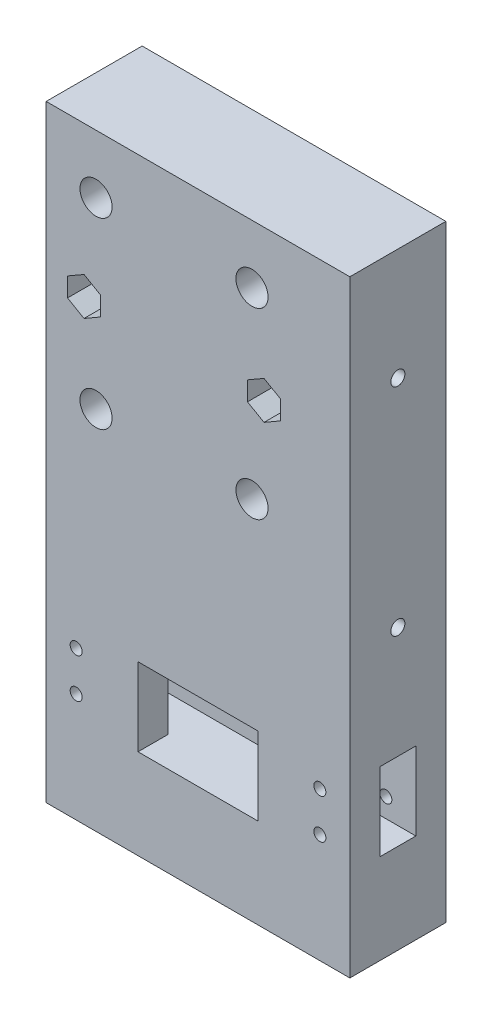
SolidWorks part; units mm, degrees
other "Markup1"
sketch "Sketch8" plane through (21.3115, 25, 0) normal (0.306, 0.1864, -0.9336) x (-0.9512, 0.0181, -0.3081)
ref_plane "Front Plane" through (0, 0, 0) normal (0, 0, 1) x (1, 0, 0)
ref_plane "Top Plane" through (0, 0, 0) normal (0, 1, 0) x (1, 0, 0)
ref_plane "Right Plane" through (0, 0, 0) normal (1, 0, 0) x (0, 0, -1)
sketch "Sketch1" plane through (0, 0, 0) normal (0, 0, 1) x (1, 0, 0)
  line L0 (0, 25) -> (0, -25) construction
  line L1 (21.3115, 25) -> (-21.3115, 25)
  line L2 (21.3115, 25) -> (21.3115, -25)
  line L3 (21.3115, -25) -> (-21.3115, -25)
  line L4 (-21.3115, 25) -> (-21.3115, -25)
  line L5 (21.3115, 25) -> (-21.3115, -25) construction
  line L6 (21.3115, -25) -> (-21.3115, 25) construction
  line L7 (-21.3115, 0) -> (21.3115, 0) construction
  circle A0 centre (-13, -15.25) radius 2.677
  circle A1 centre (13, -15.25) radius 2.677
  circle A2 centre (13, 15.25) radius 2.677
  circle A3 centre (-13, 15.25) radius 2.677
  point P0 (0, 0)
  dimension "D1" = 30.5
  dimension "D2" = 26
  dimension "D3" = 50
extrude "Boss-Extrude1" add sketch "Sketch1" along normal blind 16
sketch "Sketch2" plane through (0, 0, 0) normal (0, 0, 1) x (1, 0, 0)
  circle A0 centre (0, 0) radius 11.04
  dimension "D1" = 22.08
extrude "Cut-Extrude2" cut sketch "Sketch2" along normal blind 11
sketch "Sketch3" plane through (0, 0, 0) normal (0, 0, -1) x (-1, 0, 0)
  line L0 (0, 0) -> (-18.0234, 0) construction
  line L1 (0, 0) -> (0, 5.0894) construction
  circle A0 centre (-15, 0) radius 1.75
  circle A1 centre (15, 0) radius 1.75
  dimension "D1" = 15
  dimension "D2" = 3.5
extrude "Cut-Extrude3" cut sketch "Sketch3" against normal blind 10
sketch "Sketch9" plane through (0, 0, 0) normal (0, 0, -1) x (-1, 0, 0)
  line L0 (0, -11.04) -> (0, 11.04) construction
  line L1 (-15, 3.1754) -> (-17.75, 1.5877)
  line L2 (-17.75, 1.5877) -> (-17.75, -1.5877)
  line L3 (-17.75, -1.5877) -> (-15, -3.1754)
  line L4 (-15, -3.1754) -> (-12.25, -1.5877)
  line L5 (-12.25, -1.5877) -> (-12.25, 1.5877)
  line L6 (-12.25, 1.5877) -> (-15, 3.1754)
  line L7 (12.25, 1.5877) -> (15, 3.1754)
  line L8 (12.25, -1.5877) -> (12.25, 1.5877)
  line L9 (15, -3.1754) -> (12.25, -1.5877)
  line L10 (17.75, -1.5877) -> (15, -3.1754)
  line L11 (17.75, 1.5877) -> (17.75, -1.5877)
  line L12 (15, 3.1754) -> (17.75, 1.5877)
  circle A0 centre (-15, 0) radius 2.75 construction
  circle A1 centre (0, 0) radius 11.04 construction
  point P1 (-17.75, 0)
  dimension "D1" = 5.5
extrude "Cut-Extrude6" cut sketch "Sketch9" against normal through all from offset 5 offset against normal yes
sketch "Sketch30" plane through (0, -25, 0) normal (0, -1, 0) x (1, 0, 0)
  line L1 (-21.3115, 16) -> (21.3115, 16)
  line L2 (-21.3115, 16) -> (-21.3115, 0)
  line L3 (-21.3115, 0) -> (21.3115, 0)
  line L4 (21.3115, 16) -> (21.3115, 0)
extrude "Boss-Extrude8" add sketch "Sketch30" along normal blind 20.23
sketch "Sketch10" plane through (0, 0, 0) normal (0, 0, 1) x (1, 0, 0)
  line L0 (21.3115, -45.23) -> (-21.3115, -45.23)
  line L2 (-21.3115, -45.23) -> (-21.3115, -61.23)
  line L3 (-21.3115, -61.23) -> (21.3115, -61.23)
  line L4 (21.3115, -61.23) -> (21.3115, -45.23)
  dimension "D1" = 16
extrude "Boss-Extrude2" add sketch "Sketch10" along normal up to surface (16 mm away) up to face at (15, 0, 16)
sketch "Sketch14" plane through (-21.3115, 0, 0) normal (-1, 0, 0) x (0, 0, 1)
  line L0 (16, -61.23) -> (0, -61.23) construction
  line L1 (5, -61.23) -> (11, -61.23)
  line L2 (5, -61.23) -> (5, -48.23)
  line L3 (5, -48.23) -> (11, -48.23)
  line L4 (11, -61.23) -> (11, -48.23)
  line L7 (0, -61.23) -> (16, -61.23) construction
  point P6 (8, -61.23)
  point P7 (8, -61.23)
  dimension "D1" = 13
  dimension "D2" = 6
extrude "Cut-Extrude7" cut sketch "Sketch14" against normal through all
sketch "Sketch16" plane through (21.3115, 0, 0) normal (1, 0, 0) x (0, 0, -1)
  line L0 (-8, -48.23) -> (-8, 25)
  line L1 (-11, -48.23) -> (-5, -48.23) construction
  line L2 (-16, 25) -> (0, 25) construction
  line L4 (-16, 25) -> (0, 25)
  line L5 (-16, 25) -> (-16, -48.23)
  line L6 (-16, -48.23) -> (0, -48.23)
  line L7 (0, 25) -> (0, -48.23)
  line M6 (-11, -48.23) -> (-5, -48.23)
  line M9 (0, -61.23) -> (0, 25)
  line M10 (0, 25) -> (-16, 25)
  line M11 (-16, 25) -> (-16, -61.23)
extrude "Boss-Extrude3" add sketch "Sketch16" along normal blind 8 contours L6 L0 M11 M6 M10 | L6 L0 M6 M9 M10 region at (21.3115, -11.615, 12) region at (21.3115, -11.615, 4)
sketch "Sketch17" plane through (29.3115, 0, 0) normal (1, 0, 0) x (0, 0, -1)
  line L0 (-8, -48.23) -> (-8, 25)
  line L1 (-16, -48.23) -> (0, -48.23) construction
  line L2 (0, 25) -> (-16, 25) construction
  line L3 (-8, -11.615) -> (0, -11.615)
  line L4 (0, -48.23) -> (0, 25) construction
  circle A0 centre (-8, 6.385) radius 1.175
  circle A1 centre (-8, -29.615) radius 1.175
  point P8 (-8, -11.615)
  dimension "D2" = 2.35
  dimension "D1" = 18
extrude "Cut-Extrude9" cut sketch "Sketch17" against normal blind 8 contours L0 A0 | L0 A0 | A1 L0 | A1 L0 region at (29.3115, -29.615, 8.4987) region at (29.3115, 6.385, 8.4987) region at (29.3115, 6.385, 7.5013) region at (29.3115, -29.615, 7.5013)
sketch "Sketch18" plane through (0, 0, 0) normal (0, 0, -1) x (-1, 0, 0)
  line L0 (-25.3115, -48.23) -> (-25.3115, 25)
  line L1 (-29.3115, -48.23) -> (-21.3115, -48.23) construction
  line L2 (-29.3115, 25) -> (21.3115, 25) construction
  line L3 (-25.3115, -11.615) -> (-29.3115, -11.615)
  line L4 (-26.2115, 8.385) -> (-24.4115, 8.385)
  line L5 (-26.2115, 8.385) -> (-26.2115, 4.385)
  line L6 (-26.2115, 4.385) -> (-24.4115, 4.385)
  line L7 (-24.4115, 8.385) -> (-24.4115, 4.385)
  line L8 (-26.2115, 8.385) -> (-24.4115, 4.385) construction
  line L9 (-26.2115, 4.385) -> (-24.4115, 8.385) construction
  line L10 (-29.3115, -48.23) -> (-29.3115, 25) construction
  line L11 (-26.2115, -27.615) -> (-24.4115, -27.615)
  line L12 (-24.4115, -31.615) -> (-24.4115, -27.615)
  line L13 (-26.2115, -31.615) -> (-24.4115, -31.615)
  line L14 (-26.2115, -31.615) -> (-26.2115, -27.615)
  point P6 (-25.3115, 6.385)
  point P11 (-25.3115, -11.615)
  dimension "D1" = 18
  dimension "D2" = 4
  dimension "D3" = 1.8
extrude "Cut-Extrude10" cut sketch "Sketch18" against normal blind 10.2 contours L7 L4 L0 L6 | L5 L6 L0 L4 | L14 L11 L12 L13 region at (25.7615, 6.385, 0) region at (24.8615, 6.385, 0)
sketch "Sketch15" plane through (0, 0, 0) normal (0, 0, -1) x (-1, 0, 0)
  line L0 (21.3115, -61.23) -> (-21.3115, -61.23) construction
  line L1 (-29.3115, -23.2996) -> (21.3115, -23.2996)
  line L2 (-21.3115, -61.23) -> (-21.3115, -48.23)
  line L3 (-29.3115, -48.23) -> (-29.3115, 25) construction
  line L4 (-4, -23.2996) -> (-4, -61.23)
  line L7 (-21.3115, -61.23) -> (-21.3115, -48.23) construction
  line L8 (-21.3115, -48.23) -> (-21.3115, -61.23) construction
  line L9 (-21.3115, -54.73) -> (21.3115, -54.73)
  line L10 (21.3115, 25) -> (21.3115, -61.23) construction
  line L11 (21.3115, -54.73) -> (21.3115, -28)
  line L12 (21.3115, -28) -> (0, -28)
  line L13 (0, -28) -> (0, -61.23)
  circle A2 centre (16.3115, -58.03) radius 1
  circle A4 centre (16.3115, -51.43) radius 1
  point P11 (-21.3115, -61.23)
  dimension "D1" = 5
  dimension "D2" = 3.2
extrude "Cut-Extrude8" cut sketch "Sketch15" against normal through all and the other way through all contours A2 | A4
sketch "Sketch6" plane through (0, -48.23, 0) normal (0, -1, 0) x (1, 0, 0)
  line L0 (21.3115, 11) -> (-21.3115, 11) construction
  line L1 (4.517, 11) -> (-4.517, 11)
  line L2 (4.517, 11) -> (4.517, 14.85)
  line L3 (4.517, 14.85) -> (-4.517, 14.85)
  line L4 (-4.517, 11) -> (-4.517, 14.85)
  line L5 (4.517, 11) -> (-4.517, 14.85) construction
  line L6 (4.517, 14.85) -> (-4.517, 11) construction
  point P0 (0, 12.925)
  dimension "D1" = 3.85
extrude "Cut-Extrude5" cut sketch "Sketch6" against normal blind 50 and the other way through all
sketch "Sketch20" plane through (0, -48.23, 0) normal (0, -1, 0) x (-1, 0, 0)
  line L1 (-21.3115, -16) -> (-29.3115, -16)
  line L2 (-21.3115, -16) -> (-21.3115, 0)
  line L3 (-21.3115, 0) -> (-29.3115, 0)
  line L4 (-29.3115, -16) -> (-29.3115, 0)
extrude "Boss-Extrude5" add sketch "Sketch20" along normal up to surface (13 mm away) up to face at (0, -61.23, 13.2125)
sketch "Sketch21" plane through (0, -61.23, 0) normal (0, -1, 0) x (-1, 0, 0)
  line L0 (-29.3115, -16) -> (-29.3115, 0) construction
  line L1 (-21.3115, -11) -> (-29.3115, -11)
  line L2 (-21.3115, -11) -> (-21.3115, -5)
  line L3 (-21.3115, -5) -> (-29.3115, -5)
  line L4 (-29.3115, -11) -> (-29.3115, -5)
extrude "Cut-Extrude11" cut sketch "Sketch21" against normal up to surface (13 mm away) up to face at (0, -48.23, 9)
sketch "Sketch22" plane through (0, 0, 0) normal (0, 0, -1) x (-1, 0, 0)
  line L0 (21.3115, -61.23) -> (-29.3115, -61.23) construction
  line L1 (-29.3115, -61.23) -> (-29.3115, 25) construction
  circle A0 centre (-24.3115, -58.03) radius 1
  circle A3 centre (-24.3115, -51.43) radius 1
  dimension "D1" = 2
  dimension "D2" = 3.2
  dimension "D3" = 5
  dimension "D4" = 6.6
  dimension "D5" = 2
  dimension "D6" = 5
extrude "Cut-Extrude12" cut sketch "Sketch22" against normal through all
sketch "Sketch24" plane through (0, -61.23, 0) normal (0, -1, 0) x (1, 0, 0)
  line L1 (-21.3115, 5) -> (29.3115, 5)
  line L2 (-21.3115, 5) -> (-21.3115, 0)
  line L3 (-21.3115, 0) -> (29.3115, 0)
  line L4 (29.3115, 5) -> (29.3115, 0)
extrude "Boss-Extrude6" add sketch "Sketch24" along normal blind 15
sketch "Sketch25" plane through (0, 0, 5) normal (0, 0, 1) x (1, 0, 0)
  line L0 (29.3115, -76.23) -> (-21.3115, -76.23) construction
  line L1 (-21.3115, -76.23) -> (29.3115, -76.23)
  line L2 (-21.3115, -76.23) -> (-21.3115, -61.23)
  line L3 (-21.3115, -61.23) -> (29.3115, -61.23)
  line L4 (29.3115, -76.23) -> (29.3115, -61.23)
extrude "Boss-Extrude7" add sketch "Sketch25" along normal up to surface (11 mm away) up to face at (23.3115, -58.03, 16)
sketch "Sketch26" plane through (0, -76.23, 0) normal (0, -1, 0) x (1, 0, 0)
  line L0 (4, 16) -> (4, 0)
  line L1 (29.3115, 16) -> (-21.3115, 16) construction
  line L2 (-21.3115, 0) -> (29.3115, 0) construction
  line L3 (4, 8) -> (-21.3115, 8)
  line L4 (-21.3115, 16) -> (-21.3115, 0) construction
  circle A0 centre (-14, 8) radius 1
  circle A1 centre (22, 8) radius 1
  dimension "D1" = 2
  dimension "D2" = 18
extrude "Cut-Extrude13" cut sketch "Sketch26" against normal blind 10 contours L3 A0 | L3 A0 | A1 region at (-14, -76.23, 7.5756) region at (-14, -76.23, 8.4244) region at (22, -76.23, 8)
sketch "Sketch27" plane through (0, 0, 0) normal (0, 0, -1) x (-1, 0, 0)
  line L0 (-24.4115, -31.615) -> (-24.4115, -27.615) construction
  line L1 (-24.0015, -71.33) -> (-20.0015, -71.33)
  line L2 (-24.0015, -71.33) -> (-24.0015, -73.13)
  line L3 (-24.0015, -73.13) -> (-20.0015, -73.13)
  line L4 (-20.0015, -71.33) -> (-20.0015, -73.13)
  line L5 (-24.0015, -71.33) -> (-20.0015, -73.13) construction
  line L6 (-24.0015, -73.13) -> (-20.0015, -71.33) construction
  line L8 (-26.2115, -31.615) -> (-24.4115, -31.615) construction
  line L12 (-29.3115, -76.23) -> (-29.3115, 25) construction
  line L13 (21.3115, -76.23) -> (-29.3115, -76.23) construction
  line L14 (-29.3115, -49.5626) -> (21.3115, -49.5626)
  line L15 (21.3115, 25) -> (21.3115, -76.23) construction
  line L16 (-4, -49.5626) -> (-4, -76.23)
  line L17 (16.0015, -73.13) -> (12.0015, -73.13)
  line L18 (12.0015, -71.33) -> (12.0015, -73.13)
  line L19 (16.0015, -71.33) -> (12.0015, -71.33)
  line L20 (16.0015, -71.33) -> (16.0015, -73.13)
  point P0 (-22.0015, -72.23)
  dimension "D1" = 7.31
  dimension "D2" = 3.1
extrude "Cut-Extrude14" cut sketch "Sketch27" against normal blind 10.2 contours L4 L1 L2 L3 | L20 L19 L18 L17 region at (22.0015, -72.23, 0) region at (-14.0015, -72.23, 0)
sketch "Sketch29" plane through (0, 0, 16) normal (0, 0, 1) x (1, 0, 0)
  line L0 (-16.3115, -51.43) -> (24.3115, -58.03)
  line L1 (24.3115, -51.43) -> (-16.3115, -58.03)
  line L2 (-16.3115, -51.43) -> (24.3115, -51.43)
  line L3 (-16.3115, -51.43) -> (-16.3115, -58.03)
  line L4 (-16.3115, -58.03) -> (24.3115, -58.03)
  line L5 (24.3115, -51.43) -> (24.3115, -58.03)
  line L7 (-6, -48.23) -> (14, -48.23)
  line L8 (-6, -48.23) -> (-6, -61.23)
  line L9 (-6, -61.23) -> (14, -61.23)
  line L10 (14, -48.23) -> (14, -61.23)
  line L11 (-6, -48.23) -> (14, -61.23) construction
  line L12 (-6, -61.23) -> (14, -48.23) construction
  circle A0 centre (-16.3115, -51.43) radius 1 construction
  point P4 (4, -54.73)
  dimension "D1" = 13
  dimension "D2" = 20
extrude "Cut-Extrude15" cut sketch "Sketch29" against normal up to surface (5 mm away) contours L10 L7 L8 L2 | L10 L2 L8 L0 L1 | L0 L8 L1 | L10 L4 L8 L9 | L10 L0 L1 L8 L4 | L10 L1 L0 region at (4, -52.718, 16) region at (-2.6667, -54.73, 16) region at (4, -49.83, 16) region at (10.6667, -54.73, 16) region at (4, -56.742, 16) region at (4, -59.63, 16) up to face at (-16.3115, -59.03, 11)
sketch "Sketch31" plane through (0, 0, 0) normal (0, 0, -1) x (-1, 0, 0)
  line L5 (-4.5, 14.04) -> (4.5, 14.04)
  line L6 (-4.5, 14.04) -> (-4.5, 8.04)
  line L7 (-4.5, -8.04) -> (4.5, -8.04)
  line L8 (-4.5, -8.04) -> (-4.5, -14.04)
  line L9 (-4.5, -14.04) -> (4.5, -14.04)
  line L10 (4.5, -8.04) -> (4.5, -14.04)
  line L11 (-4.5, -8.04) -> (4.5, -14.04) construction
  line L12 (-4.5, -14.04) -> (4.5, -8.04) construction
  line L13 (-4.5, 8.04) -> (4.5, 8.04)
  line L14 (4.5, 14.04) -> (4.5, 8.04)
  line L15 (-4.5, 14.04) -> (4.5, 8.04) construction
  line L16 (-4.5, 8.04) -> (4.5, 14.04) construction
  circle A1 centre (0, 0) radius 11.04 construction
  point P0 (-11.04, 0)
  point P1 (0, 11.04)
  point P8 (0, -11.04)
  dimension "D1" = 6
  dimension "D2" = 9
  dimension "D3" = 9
  dimension "D4" = 6
extrude "Cut-Extrude16" cut sketch "Sketch31" against normal up to surface (11 mm away) up to face at (0, 1.1266, 11)
